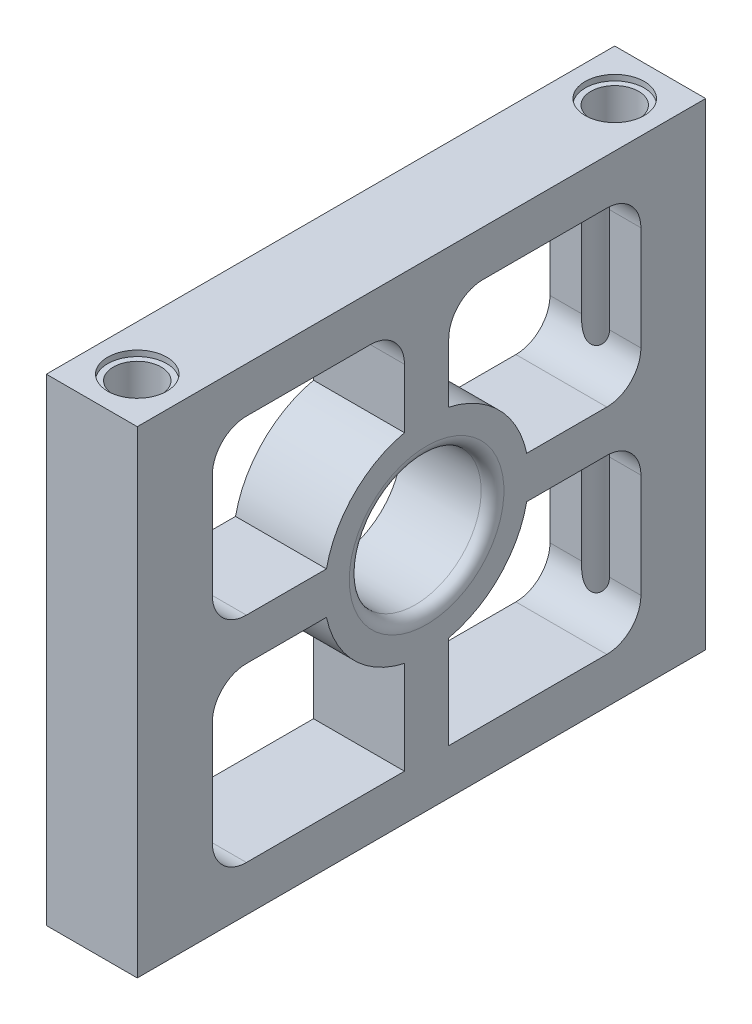
SolidWorks part; units mm, degrees
ref_plane "Front Plane" through (0, 0, 0) normal (0, 0, 1) x (1, 0, 0)
ref_plane "Top Plane" through (0, 0, 0) normal (0, 1, 0) x (1, 0, 0)
ref_plane "Right Plane" through (0, 0, 0) normal (1, 0, 0) x (0, 0, -1)
sketch "Sketch1" plane through (0, 0, 0) normal (0, 1, 0) x (1, 0, 0)
  line L1 (-10.223, 36.3848) -> (14.777, 36.3848)
  line L2 (-10.223, 36.3848) -> (-10.223, -13.6152)
  line L3 (-10.223, -13.6152) -> (14.777, -13.6152)
  line L4 (14.777, 36.3848) -> (14.777, -13.6152)
  circle A0 centre (1.277, 11.3848) radius 3.4
  dimension "D3" = 6.8
  dimension "D1" = 50
  dimension "D2" = 25
  dimension "D4" = 13.5
  dimension "D5" = 25
extrude "Boss-Extrude1" add sketch "Sketch1" along normal blind 3
sketch "Sketch2" plane through (-10.223, 0, 0) normal (-1, 0, 0) x (0, 0, 1)
  line L0 (18.15, 0) -> (-18.15, 0) construction
  line L1 (-36.3848, 3) -> (13.6152, 3)
  line L2 (-36.3848, 3) -> (-36.3848, 0)
  line L3 (-36.3848, 0) -> (13.6152, 0)
  line L4 (13.6152, 3) -> (13.6152, 0)
  line L5 (13.6152, 3) -> (13.6152, 0) construction
extrude "Boss-Extrude2" add sketch "Sketch2" along normal blind 8
sketch "Sketch3" plane through (0, 0, 0) normal (0, -1, 0) x (1, 0, 0)
  line L0 (-18.223, 13.6152) -> (14.777, 13.6152) construction
  line L1 (-18.223, -36.3848) -> (-10.223, -36.3848)
  line L2 (-18.223, -36.3848) -> (-18.223, 13.6152)
  line L3 (-18.223, 13.6152) -> (-10.223, 13.6152)
  line L4 (-10.223, -36.3848) -> (-10.223, 13.6152)
  dimension "D1" = 8
extrude "Boss-Extrude3" add sketch "Sketch3" along normal blind 42
sketch "Sketch4" plane through (0, 3, 0) normal (0, 1, 0) x (1, 0, 0)
  line L0 (-18.223, -13.6152) -> (-18.223, 36.3848) construction
  line L1 (14.777, 36.3848) -> (-18.223, 36.3848) construction
  line L2 (-18.223, -13.6152) -> (14.777, -13.6152) construction
  circle A0 centre (-14.223, 32.3848) radius 2.65
  circle A1 centre (-14.223, -9.6152) radius 2.65
  dimension "D2" = 5.3
  dimension "D4" = 5.3
  dimension "D5" = 4
  dimension "D6" = 4
  dimension "D1" = 4
  dimension "D3" = 4
extrude "Cut-Extrude1" cut sketch "Sketch4" against normal blind 0.5
ref_plane "Plane1" through (0, -19.5, 0) normal (0, 1, 0) x (1, 0, 0)
mirror "Mirror1" about plane through (0, -19.5, 0) normal (0, 1, 0) of "Cut-Extrude1"
sketch "Sketch5" plane through (-18.223, 0, 0) normal (-1, 0, 0) x (0, 0, 1)
  line L0 (18.15, 0) -> (-18.15, 0) construction
  line L1 (-6.9841, -24.1818) -> (-6.6547, -18.3888) construction
  line L2 (-6.6547, -18.3888) -> (-11.5069, -15.207) construction
  line L3 (-11.5069, -15.207) -> (-16.6885, -17.8182) construction
  line L4 (-16.6885, -17.8182) -> (-17.0179, -23.6112) construction
  line L5 (-17.0179, -23.6112) -> (-12.1657, -26.793) construction
  line L6 (-12.1657, -26.793) -> (-6.9841, -24.1818) construction
  circle A0 centre (-11.8363, -21) radius 5.025 construction
  circle A1 centre (-11.8363, -21) radius 5.8024
  dimension "D1" = 21
  dimension "D2" = 10.05
extrude "Cut-Extrude2" cut sketch "Sketch5" against normal blind 9
fillet "Fillet2" radius 1 1 edges at (-10.223, -21, -6.0339)
ref_plane "Plane2" through (-1.723, 0, 0) normal (-1, 0, 0) x (0, 0, 1)
mirror "Mirror2" about plane through (-1.723, 0, 0) normal (-1, 0, 0) of "Cut-Extrude1"
sketch "Sketch6" plane through (0, 3, 0) normal (0, 1, 0) x (1, 0, 0)
  line L0 (1.277, 14.7848) -> (1.277, 7.9848) construction
  line L1 (14.777, -13.6152) -> (14.777, 36.3848) construction
  line L2 (14.777, 16.9444) -> (14.777, 5.8251)
  circle A0 centre (1.277, 11.3848) radius 3.4 construction
  circle A1 centre (1.277, 11.3848) radius 3.1
  circle A2 centre (1.277, 11.3848) radius 12.6
  arc A3 (14.777, 16.9444) -> (14.777, 5.8251) centre (1.277, 11.3848) ccw
  line M9 (14.777, -13.6152) -> (14.777, 36.3848)
  dimension "D1" = 25.2
  dimension "D2" = 2
extrude "Boss-Extrude4" add sketch "Sketch6" along normal blind 2 contours A3 A2 M9
fillet "Fillet4" radius 1 1 edges at (14.777, 5, -11.3848)
sketch "Sketch8" plane through (0, 3, 0) normal (0, 1, 0) x (1, 0, 0)
  line L0 (4.677, 11.3848) -> (-2.123, 11.3848) construction
  circle A0 centre (1.277, 11.3848) radius 3.4 construction
  circle A1 centre (1.277, 19.8848) radius 1.5898
  circle A2 centre (1.277, 2.8848) radius 1.7774
  point P9 (1.277, 11.3848)
  dimension "D1" = 8.5
  dimension "D2" = 8.5
extrude "Cut-Extrude3" cut sketch "Sketch8" against normal blind 10
sketch "Sketch9" plane through (0, 0, 13.6152) normal (0, 0, 1) x (1, 0, 0)
  line L1 (14.777, 0) -> (-34.2447, 0)
  line L2 (14.777, 0) -> (14.777, 20.9769)
  line L3 (14.777, 20.9769) -> (-34.2447, 20.9769)
  line L4 (-34.2447, 0) -> (-34.2447, 20.9769)
extrude "Cut-Extrude4" cut sketch "Sketch9" against normal through all
ref_plane "Plane3" through (0, 0, -11.3848) normal (0, 0, 1) x (1, 0, 0)
sketch "Sketch11" plane through (0, 0, 0) normal (0, 1, 0) x (1, 0, 0)
  circle A2 centre (-14.223, 32.3848) radius 2.1
  dimension "D1" = 4.2
extrude "Cut-Extrude5" cut sketch "Sketch11" against normal through all contours A2
mirror "Mirror3" about plane through (0, 0, -11.3848) normal (0, 0, 1) of "Cut-Extrude5"
sketch "Sketch14" plane through (0, 0, 0) normal (0, 1, 0) x (1, 0, 0)
  circle A0 centre (-14.223, -9.6152) radius 2.6
  dimension "D1" = 5.2
extrude "Cut-Extrude6" cut sketch "Sketch14" against normal blind 0.5
mirror "Mirror4" about plane through (0, 0, -11.3848) normal (0, 0, 1) of "Cut-Extrude6"
sketch "Sketch15" plane through (-10.223, 0, 0) normal (1, 0, 0) x (0, 0, -1)
  line L0 (-7.0152, -7) -> (-7.0152, -16.1557)
  line L1 (-4.0152, -19.1557) -> (3.0273, -19.1557)
  line L2 (-4.0152, -4) -> (6.8886, -4)
  line L3 (9.8886, -7) -> (9.8886, -12.2133)
  line L4 (36.3848, 0) -> (-13.6152, 0) construction
  line L5 (11.8363, -42) -> (11.8363, 0) construction
  line L8 (11.8363, -21) -> (36.3848, -21) construction
  line L10 (36.3848, -42) -> (36.3848, 0) construction
  line L11 (13.7839, -7) -> (13.7839, -12.2133)
  line L12 (27.6878, -4) -> (16.7839, -4)
  line L13 (27.6878, -19.1557) -> (20.6453, -19.1557)
  line L14 (30.6878, -7) -> (30.6878, -16.1557)
  line L15 (-7.0152, -4) -> (-7.0152, -19.1557)
  line L16 (-7.0152, -19.1557) -> (3.0273, -19.1557)
  line L17 (-7.0152, -4) -> (9.8886, -4)
  line L18 (9.8886, -4) -> (9.8886, -12.2133)
  line L19 (13.7839, -4) -> (13.7839, -12.2133)
  line L20 (30.6878, -4) -> (13.7839, -4)
  line L21 (30.6878, -19.1557) -> (20.6453, -19.1557)
  line L22 (30.6878, -4) -> (30.6878, -19.1557)
  line L23 (30.6878, -35) -> (30.6878, -25.8443)
  line L24 (27.6878, -22.8443) -> (20.6453, -22.8443)
  line L25 (27.6878, -38) -> (13.7839, -38)
  line L26 (13.7839, -38) -> (13.7839, -29.7867)
  line L27 (9.8886, -38) -> (9.8886, -29.7867)
  line L28 (-4.0152, -38) -> (9.8886, -38)
  line L29 (-4.0152, -22.8443) -> (3.0273, -22.8443)
  line L30 (-7.0152, -35) -> (-7.0152, -25.8443)
  line L31 (30.6878, -38) -> (30.6878, -22.8443)
  line L32 (30.6878, -22.8443) -> (20.6453, -22.8443)
  line L33 (30.6878, -38) -> (13.7839, -38)
  line L34 (13.7839, -38) -> (13.7839, -29.7867)
  line L35 (9.8886, -38) -> (9.8886, -29.7867)
  line L36 (-7.0152, -38) -> (9.8886, -38)
  line L37 (-7.0152, -22.8443) -> (3.0273, -22.8443)
  line L38 (-7.0152, -38) -> (-7.0152, -22.8443)
  circle A1 centre (11.8363, -21) radius 9
  arc A3 (6.8886, -4) -> (9.8886, -7) centre (6.8886, -7) cw
  arc A4 (-7.0152, -7) -> (-4.0152, -4) centre (-4.0152, -7) cw
  arc A5 (-7.0152, -16.1557) -> (-4.0152, -19.1557) centre (-4.0152, -16.1557) ccw
  arc A6 (-4.0152, -22.8443) -> (-7.0152, -25.8443) centre (-4.0152, -25.8443) ccw
  arc A7 (-4.0152, -38) -> (-7.0152, -35) centre (-4.0152, -35) cw
  arc A8 (30.6878, -35) -> (27.6878, -38) centre (27.6878, -35) cw
  arc A9 (30.6878, -25.8443) -> (27.6878, -22.8443) centre (27.6878, -25.8443) ccw
  arc A10 (27.6878, -19.1557) -> (30.6878, -16.1557) centre (27.6878, -16.1557) ccw
  arc A11 (27.6878, -4) -> (30.6878, -7) centre (27.6878, -7) cw
  arc A12 (13.7839, -7) -> (16.7839, -4) centre (16.7839, -7) cw
  point P31 (0, 0)
  dimension "D2" = 18
  dimension "D3" = 3
  dimension "D4" = 3
  dimension "D1" = 4
extrude "Cut-Extrude7" cut sketch "Sketch15" against normal blind 10 contours L0 A5 L1 A1 L3 A3 L2 A4 | A12 L11 A1 L13 A10 L14 A11 L12 | L23 A9 L24 A1 L26 L25 A8 | A7 L28 L27 A1 L29 A6 L30
